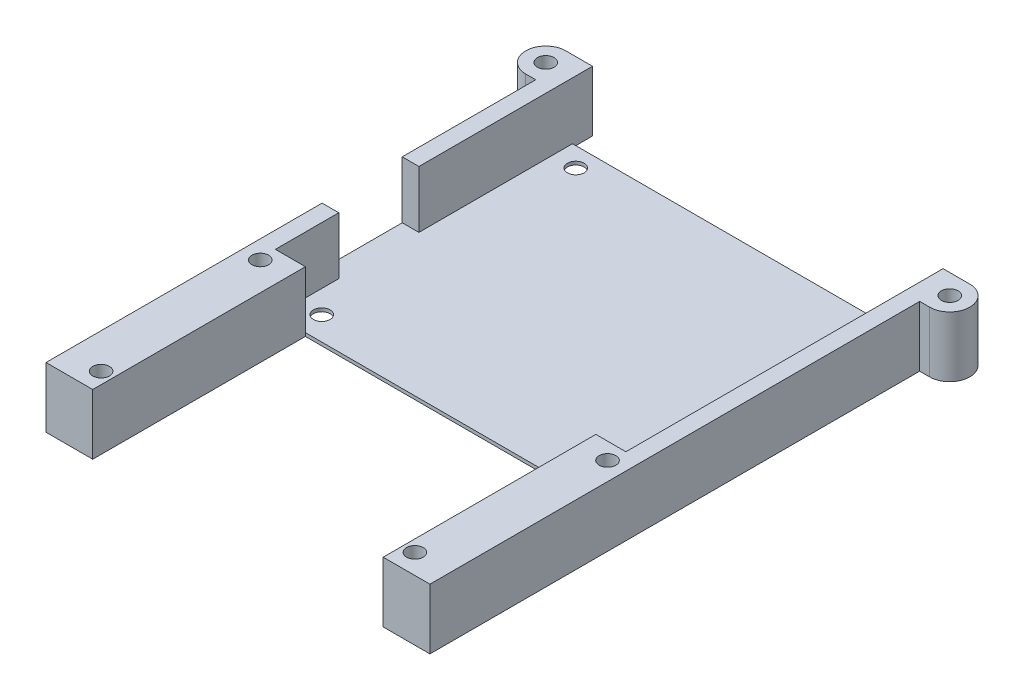
SolidWorks part; units mm, degrees
ref_plane "Front Plane" through (0, 0, 0) normal (0, 0, 1) x (1, 0, 0)
ref_plane "Top Plane" through (0, 0, 0) normal (0, 1, 0) x (1, 0, 0)
ref_plane "Right Plane" through (0, 0, 0) normal (1, 0, 0) x (0, 0, -1)
sketch "Sketch1" plane through (0, 0, 0) normal (0, 1, 0) x (1, 0, 0)
  line L0 (0, 0) -> (0, 76.35) construction
  line L1 (-28.75, 76.35) -> (28.75, 76.35)
  line L2 (28.75, 76.35) -> (28.75, 0)
  line L3 (28.75, 0) -> (21.75, 0)
  line L4 (21.75, 0) -> (21.75, 31.85)
  line L5 (21.75, 31.85) -> (-21.75, 31.85)
  line L6 (-21.75, 31.85) -> (-21.75, 0)
  line L7 (-21.75, 0) -> (-28.75, 0)
  line L8 (-28.75, 0) -> (-28.75, 76.35)
  line L9 (-26.25, 76.35) -> (-26.25, 31.85)
  line L14 (-26.25, 31.85) -> (-21.75, 31.85)
  line L15 (26.25, 76.35) -> (26.25, 31.85)
  line L16 (26.25, 31.85) -> (21.75, 31.85)
  line L17 (28.75, 79.35) -> (30.25, 79.35)
  line L18 (-28.75, 41.35) -> (-26.25, 41.35)
  line L19 (-28.75, 41.35) -> (-28.75, 53.35)
  line L20 (-28.75, 53.35) -> (-26.25, 53.35)
  line L21 (-26.25, 41.35) -> (-26.25, 53.35)
  line L22 (30.25, 73.35) -> (28.75, 73.35)
  line L23 (-30.25, 73.35) -> (-28.75, 73.35)
  line L24 (-28.75, 79.35) -> (-30.25, 79.35)
  line L25 (26.25, 76.35) -> (26.25, 79.35)
  line L26 (26.25, 79.35) -> (28.75, 79.35)
  line L28 (-28.75, 76.35) -> (-28.75, 79.35)
  line L29 (-28.75, 79.35) -> (-26.25, 79.35)
  line L30 (-26.25, 79.35) -> (-26.25, 76.35)
  arc A0 (30.25, 73.35) -> (30.25, 79.35) centre (30.25, 76.35) ccw
  arc A1 (-30.25, 73.35) -> (-30.25, 79.35) centre (-30.25, 76.35) cw
  point P10 (0, 76.35)
  point P16 (-27.5, 41.35)
  point P17 (-22.85, 73.45)
  point P18 (22.85, 73.45)
  point P23 (22.85, 35.4)
  point P24 (-22.85, 35.4)
  point P25 (23.5, 3)
  point P26 (26, 29.35)
  point P27 (-26, 29.35)
  point P28 (-23.5, 3)
  point P40 (30.25, 76.35)
  point P41 (-30.25, 76.35)
  dimension "D16" = 3
  dimension "D1" = 2.5
  dimension "D2" = 7
  dimension "D3" = 43.5
  dimension "D4" = 31.85
  dimension "D5" = 44.5
  dimension "D6" = 23
  dimension "D7" = 12
  dimension "D8" = 22.85
  dimension "D9" = 38.05
  dimension "D10" = 2.9
  dimension "D11" = 47
  dimension "D12" = 52
  dimension "D13" = 47
  dimension "D14" = 3
  dimension "D15" = 1.5
extrude "Boss-Extrude1" add sketch "Sketch1" along normal blind 0.5 contours L5 L0 L1 L9 L14 | L0 L5 L16 L15 L1 | L20 L8 L18 L9 region at (-13.125, 0, -54.1) region at (13.125, 0, -54.1) region at (-27.5, 0, -47.35)
extrude "Boss-Extrude2" add sketch "Sketch1<3>" along normal blind 9.05 contours L18 L8 L7 L6 L14 L9 | L8 L20 L9 L1 | L15 L16 L4 L3 L2 L1 | A1 L23 L8 L24 | L22 A0 L17 L2 | L26 L25 L1 | L30 L29 L28 L1 region at (-27.5, 0, -77.85) region at (-27.5, 0, -64.85) region at (-30.7362, 0, -76.35) region at (29.944, 0, -76.7172) region at (25.999, 0, -28.6329) region at (-25.4666, 0, -17.9154)
sketch "Sketch1<3>" plane through (0, 0, 0) normal (0, 1, 0) x (1, 0, 0) same geometry as "Sketch1"
hole_wizard "Ø2.5 (2.5) Diameter Hole1" positions "Sketch4" profile "Sketch5" hole size "Ø2.5" standard "ANSI Metric"
sketch "Sketch4" plane through (0, 0, 0) normal (0, -1, 0) x (-1, 0, 0)
  point P0 (-22.85, 73.45)
  point P3 (22.85, 73.45)
  point P6 (26, 29.35)
  point P9 (22.85, 35.4)
  point P12 (-22.85, 35.4)
  point P15 (-26, 29.35)
  point P18 (-23.5, 3)
  point P21 (23.5, 3)
  point P24 (-30.25, 76.35)
  point P27 (30.25, 76.35)
sketch "Sketch5" plane through (22.85, 0, -73.45) normal (1, 0, 0) x (0, 0, -1)
  line L0 (0, 0) -> (0, 12.7511)
  line L1 (0, 12.7511) -> (1.25, 12)
  line L2 (1.25, 12) -> (1.25, 0)
  line L5 (1.25, 0) -> (0, 0)
  line L10 (0, 12.7511) -> (-1.25, 12) construction
  line L11 (0, -6.35) -> (0, 107.95) construction
  dimension "Hole Dia." = 2.5
  dimension "Hole Depth" = 12
  dimension "Drill Angle" = 118
